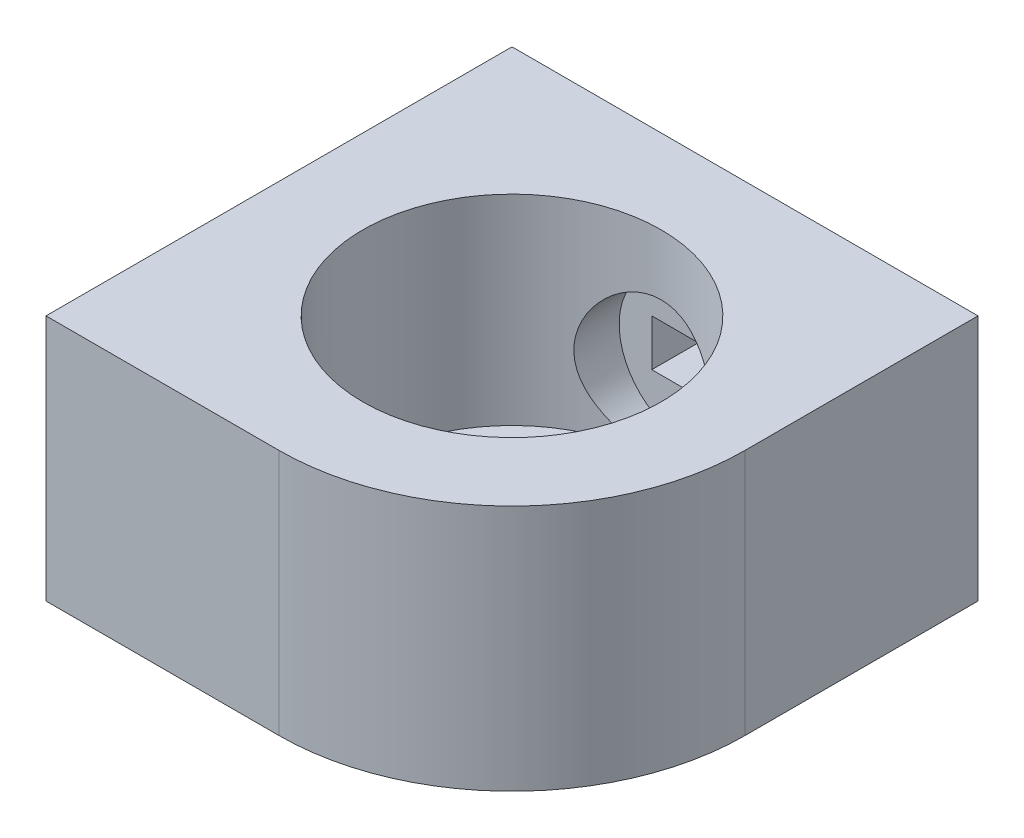
SolidWorks part; units mm, degrees
ref_plane "Front Plane" through (0, 0, 0) normal (0, 0, 1) x (1, 0, 0)
ref_plane "Top Plane" through (0, 0, 0) normal (0, 1, 0) x (1, 0, 0)
ref_plane "Right Plane" through (0, 0, 0) normal (1, 0, 0) x (0, 0, -1)
sketch "Sketch1" plane through (0, 0, 0) normal (0, 1, 0) x (1, 0, 0)
  line L0 (0, 25) -> (-25, 25)
  line L1 (-25, 25) -> (-25, 0)
  line L2 (0, -25) -> (-25, -25)
  line L3 (-25, -25) -> (-25, 0)
  line L4 (0, 25) -> (25, 25)
  line L5 (25, 25) -> (25, 0)
  circle A0 centre (0, 0) radius 16
  circle A1 centre (0, 0) radius 25
  dimension "D1" = 32
  dimension "D2" = 50
extrude "Boss-Extrude1" add sketch "Sketch1" along normal blind 26.5 contours A1 A0 | A1 L3 L2 | A1 L0 L1 | A1 L5 L4 region at (-19.4158, 0, -19.4158) region at (19.4158, 0, -19.4158) region at (17.1777, 0, -17.1777) region at (-19.4158, 0, 19.4158)
extrude "Boss-Extrude2" add sketch "Sketch1<3>" along normal blind 5 contours A0 region at (0, 0, 0)
sketch "Sketch1<3>" plane through (0, 0, 0) normal (0, 1, 0) x (1, 0, 0) same geometry as "Sketch1"
sketch "Sketch2" plane through (0, 5, 0) normal (0, 1, 0) x (1, 0, 0)
  circle A0 centre (0, 0) radius 2
  dimension "D1" = 4
extrude "Cut-Extrude1" cut sketch "Sketch2" against normal blind 5
sketch "Sketch3" plane through (-25, 0, 0) normal (-1, 0, 0) x (0, 0, 1)
  line L0 (-13.0444, 26.5) -> (-13.0444, 0) construction
  line L1 (-25, 26.5) -> (25, 26.5) construction
  line L2 (55, 0) -> (-55, 0) construction
  line L3 (0, -55) -> (0, 55) construction
  circle A0 centre (0, 15) radius 2.55
  dimension "D1" = 5.1
extrude "Cut-Extrude2" cut sketch "Sketch3" against normal blind 5
sketch "Sketch5" plane through (0, 0, 0) normal (0, 0, 1) x (1, 0, 0)
  line L0 (0, -55) -> (0, 55) construction
  line L1 (16, 5) -> (-16, 5) construction
  circle A0 centre (0, 12.5) radius 7.5
  dimension "D1" = 15
extrude "Cut-Extrude8" cut sketch "Sketch5" against normal blind 19
sketch "Sketch6" plane through (0, 0, -19) normal (0, 0, 1) x (1, 0, 0)
  line L1 (-4, 10) -> (4, 10)
  line L2 (-4, 10) -> (-4, 15)
  line L3 (-4, 15) -> (4, 15)
  line L4 (4, 10) -> (4, 15)
  line L5 (-4, 10) -> (4, 15) construction
  line L6 (-4, 15) -> (4, 10) construction
  circle A0 centre (0, 12.5) radius 7.5 construction
  dimension "D1" = 5
  dimension "D2" = 8
extrude "Cut-Extrude9" cut sketch "Sketch6" against normal blind 19
